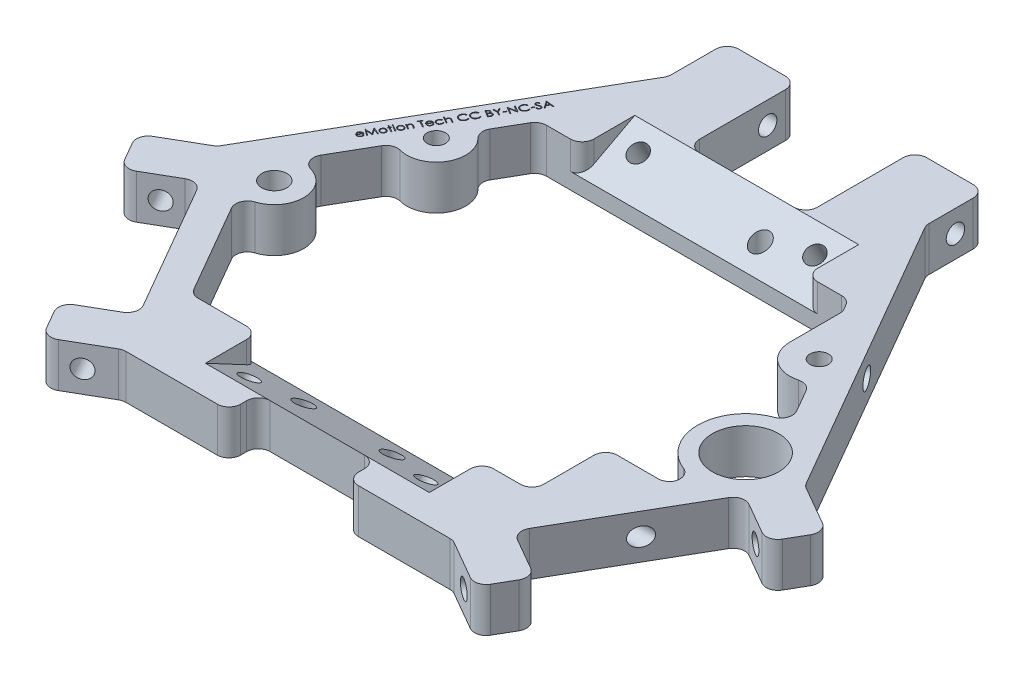
SolidWorks part; units mm, degrees
material "Alliage 1060"
ref_plane "Plan de face" through (0, 0, 0) normal (0, 0, 1) x (1, 0, 0)
ref_plane "Plan de dessus" through (0, 0, 0) normal (0, 1, 0) x (1, 0, 0)
ref_plane "Plan de droite" through (0, 0, 0) normal (1, 0, 0) x (0, 0, -1)
ref_axis "Axe1" through (0, 0, 0) along (0, 1, 0)
sketch "Esquisse2" plane through (0, 0, 0) normal (0, 1, 0) x (1, 0, 0)
  line L0 (17.5, 44) -> (-17.5, 44)
  line L1 (-17.5, 44) -> (-17.5, 36)
  line L2 (-17.5, 36) -> (-39.9269, -2.8446)
  line L3 (-39.9269, -2.8446) -> (-46.8551, -6.8446)
  line L4 (-46.8551, -6.8446) -> (-29.3551, -37.1554)
  line L5 (-29.3551, -37.1554) -> (-22.4269, -33.1554)
  line L6 (-22.4269, -33.1554) -> (22.4269, -33.1554)
  line L7 (0, 54.3424) -> (0, -64.0626) construction
  line L8 (17.5, 40) -> (-17.5, 40) construction
  line L10 (-28.7135, 16.5777) -> (21.5714, -12.4543) construction
  line L11 (20.1175, -29.1554) -> (-20.1175, -29.1554)
  line L12 (-20.1175, -29.1554) -> (-35.3081, -2.8446)
  line L13 (-35.3081, -2.8446) -> (-15.1906, 32)
  line L14 (-15.1906, 32) -> (15.1906, 32)
  line L16 (28.7135, 16.5777) -> (-21.5714, -12.4543) construction
  line L18 (35.3081, -2.8446) -> (15.1906, 32)
  line L19 (20.1175, -29.1554) -> (35.3081, -2.8446)
  line L20 (29.3551, -37.1554) -> (22.4269, -33.1554)
  line L21 (46.8551, -6.8446) -> (29.3551, -37.1554)
  line L22 (39.9269, -2.8446) -> (46.8551, -6.8446)
  line L23 (17.5, 36) -> (39.9269, -2.8446)
  line L24 (17.5, 44) -> (17.5, 36)
  dimension "D8" = 40
  dimension "D2" = 12
  dimension "D3" = 120
  dimension "D4" = 120
  dimension "D5" = 8
  dimension "D6" = 35
  dimension "D7" = 35
  dimension "D9" = 12
  dimension "D10" = 4
  dimension "D11" = 4
extrude "Boss.-Extru.2" add sketch "Esquisse2" along normal blind 6 contours L2 L3 L4 L5 L6 L20 L21 L22 L23 L24 L0 L1 | L13 L14 L18 L19 L11 L12
hole_wizard "Trou pour taraudage pour trou taraudé M32" positions "Esquisse6" profile "Esquisse5" hole size "M3" standard "ISO"
sketch "Esquisse6" plane through (-17.5, 0, 0) normal (-1, 0, 0) x (0, 0, 1)
  line L4 (-40, 0) -> (-40, 6) construction
  line L5 (-44, 0) -> (-36, 0) construction
  line L6 (-44, 6) -> (-36, 6) construction
  point P0 (-40, 3)
sketch "Esquisse5" plane through (-17.5, 3, -40) normal (0, 1, 0) x (0, 0, 1)
  line L0 (0, 0) -> (0, 10.7511)
  line L1 (0, 10.7511) -> (1.25, 10)
  line L2 (1.25, 10) -> (1.25, 0)
  line L5 (1.25, 0) -> (0, 0)
  line L10 (0, 10.7511) -> (-1.25, 10) construction
  line L11 (0, -6.35) -> (0, 107.95) construction
  dimension "Diamètre du perçage" = 2.5
  dimension "Profondeur du perçage" = 10
  dimension "Angle de pointe" = 118
mirror "Symétrie1" about plane through (0, 0, 0) normal (1, 0, 0) of "Trou pour taraudage pour trou taraudé M32"
pattern_circular "Répétition circulaire1" count 3 over 360 about axis through (0, 0, 0) along (0, 1, 0) of "Trou pour taraudage pour trou taraudé M32", "Symétrie1"
sketch "Esquisse8" plane through (0, 0, 0) normal (1, 0, 0) x (0, 0, -1)
  line L0 (-33.1554, 6) -> (-29.1554, 6)
  line L1 (-29.1554, 6) -> (-22, 2.1954)
  line L2 (-22, 2.1954) -> (-22, 0)
  line L3 (-33.1554, 0) -> (-33.1554, 6)
  line L5 (0, 0) -> (0, 21.2084) construction
  line L6 (33.1554, 0) -> (33.1554, 6)
  line L8 (29.1554, 6) -> (22, 2.1954)
  line L9 (33.1554, 6) -> (29.1554, 6)
  line L10 (-22, 0) -> (-33.1554, 0)
  line L11 (-6.8446, 0) -> (-37.1554, 0) construction
  line L12 (22, 0) -> (33.1554, 0)
  line L13 (22, 2.1954) -> (22, 0)
  dimension "D1" = 28
  dimension "D2" = 22
extrude "Boss.-Extru.3" add sketch "Esquisse8" along normal blind 15.2 and the other way blind 15.2
hole_wizard "Trou pour taraudage pour trou taraudé M33" positions "Esquisse11" profile "Esquisse10" hole size "M3" standard "ISO"
sketch "Esquisse11" plane through (0, -7.4079, -3.9389) normal (0, 0.8829, 0.4695) x (1, 0, 0)
  line L0 (-15.2, 20.4555) -> (15.2, 20.4555) construction
  line L1 (0, 0) -> (0, 21.5167) construction
  line L2 (0, 0) -> (0, 40.3955) construction
  point P2 (12, 25.4555)
  point P17 (-12, 25.4555)
  dimension "D1" = 5
  dimension "D2" = 12
sketch "Esquisse10" plane through (12, 4.5427, -26.4147) normal (1, 0, 0) x (0, -0.4695, 0.8829)
  line L0 (0, 0) -> (0, 10.7511)
  line L1 (0, 10.7511) -> (1.25, 10)
  line L2 (1.25, 10) -> (1.25, 0)
  line L5 (1.25, 0) -> (0, 0)
  line L10 (0, 10.7511) -> (-1.25, 10) construction
  line L11 (0, -6.35) -> (0, 107.95) construction
  dimension "Diamètre du perçage" = 2.5
  dimension "Profondeur du perçage" = 10
  dimension "Angle de pointe" = 118
sketch "Esquisse9" plane through (0, 6, 0) normal (0, 1, 0) x (1, 0, 0)
  line L0 (-8, 29.1554) -> (-8, 44)
  line L1 (0, 0) -> (74.807, 0) construction
  line L2 (17.5, 44) -> (-17.5, 44) construction
  line L3 (-8, 44) -> (8, 44)
  line L4 (8, 44) -> (8, 29.1554)
  line L5 (15.2, 29.1554) -> (-15.2, 29.1554) construction
  line L6 (8, 29.1554) -> (-8, 29.1554)
  line L7 (8, -44) -> (8, -29.1554)
  line L8 (-8, -44) -> (8, -44)
  line L9 (-8, -29.1554) -> (-8, -44)
  line L10 (8, -29.1554) -> (-8, -29.1554)
  line L16 (0, 44) -> (0, -44) construction
  dimension "D2" = 16
extrude "Enlèv. mat.-Extru.1" cut sketch "Esquisse9" against normal blind 15
sketch "Esquisse12" plane through (0, 6, 0) normal (0, 1, 0) x (1, 0, 0)
  line L0 (15.2, -22) -> (24.2487, -22)
  line L1 (20.1175, -29.1554) -> (35.3081, -2.8446) construction
  line L2 (-20.1175, -29.1554) -> (-15.2, -29.1554)
  line L3 (-15.2, -29.1554) -> (-15.2, -22)
  line L4 (0, 0) -> (0, -39.258) construction
  line L5 (15.2, -29.1554) -> (15.2, -22)
  line L6 (20.1175, -29.1554) -> (15.2, -29.1554)
  line L7 (24.2487, -22) -> (20.1175, -29.1554)
  line L8 (-15.2, -22) -> (-24.2487, -22)
  line L9 (15.2, 22) -> (-15.2, 22) construction
  line L10 (-20.1175, -29.1554) -> (-35.3081, -2.8446) construction
  line L11 (-24.2487, -22) -> (-20.1175, -29.1554)
  line L12 (-15.2, 22) -> (-15.2, 31.9837)
  line L13 (-15.2, 31.9837) -> (-20.9641, 22)
  line L14 (-35.3081, -2.8446) -> (-15.2, 31.9837) construction
  line L15 (-20.9641, 22) -> (-15.2, 22)
  line L17 (15.2, 31.9837) -> (20.9641, 22)
  line L18 (35.3081, -2.8446) -> (15.2, 31.9837) construction
  line L19 (20.9641, 22) -> (15.2, 22)
  line L20 (15.2, 22) -> (15.2, 31.9837)
  line L22 (15.2, -22) -> (-15.2, -22) construction
extrude "Boss.-Extru.4" add sketch "Esquisse12" against normal up to surface (6 mm away) up to face at (12, 0, -27.4144)
mirror "Symétrie2" about plane through (0, 0, 0) normal (0, 0, 1) of "Trou pour taraudage pour trou taraudé M33"
hole_wizard "Trou pour taraudage pour trou taraudé M34" positions "Esquisse21" profile "Esquisse20" hole size "M3" standard "ISO"
sketch "Esquisse21" plane through (0, 6, 0) normal (0, 1, 0) x (1, 0, 0)
  line L0 (0, 0) -> (27.2651, 0) construction
  point P64 (-6, -25)
  point P66 (6, -25)
  point P75 (6, 25)
  dimension "D1" = 25
  dimension "D4" = 6
  dimension "D5" = 6
  dimension "D6" = 25
sketch "Esquisse20" plane through (-6, 6, 25) normal (1, 0, 0) x (0, 0, 1)
  line L0 (0, 0) -> (0, 15.7511)
  line L1 (0, 15.7511) -> (1.25, 15)
  line L2 (1.25, 15) -> (1.25, 0)
  line L5 (1.25, 0) -> (0, 0)
  line L10 (0, 15.7511) -> (-1.25, 15) construction
  line L11 (0, -6.35) -> (0, 107.95) construction
  dimension "Diamètre du perçage" = 2.5
  dimension "Profondeur du perçage" = 15
  dimension "Angle de pointe" = 118
sketch "Esquisse22" plane through (0, 0, 0) normal (0, -1, 0) x (1, 0, 0)
  line L0 (22, -20.2058) -> (22, -13)
  line L1 (-35.3081, 2.8446) -> (-33.1937, -0.8177)
  line L2 (24.2487, 22) -> (35.3081, 2.8446) construction
  line L3 (28.119, -9.6074) -> (22, -20.2058)
  line L4 (30.0222, 12) -> (22, 12)
  line L5 (24.2487, 22) -> (35.3081, 2.8446) construction
  line L6 (22, 12) -> (22, 22)
  line L8 (22, 22) -> (24.2487, 22)
  line L9 (24.2487, 22) -> (30.0222, 12)
  line L10 (21.5, -17) -> (-12.566, -17) construction
  line L11 (22, 17) -> (-17.9641, 17) construction
  line L12 (0, 0) -> (0, -37.0001) construction
  line L13 (-35.3081, 2.8446) -> (-20.9641, -22) construction
  line L14 (-32.9792, 6.8783) -> (-35.3081, 2.8446)
  line L15 (-28.119, -9.6074) -> (-24.1214, -16.5314)
  line L16 (35.3081, 2.8446) -> (20.9641, -22) construction
  line L17 (31.4777, 9.479) -> (35.3081, 2.8446)
  line L18 (35.3081, 2.8446) -> (31.6505, -3.4906)
  line L19 (24.2487, 22) -> (15.2, 22) construction
  line L20 (-24.2487, 22) -> (-35.3081, 2.8446) construction
  arc A0 (-28.119, -9.6074) -> (-24.1214, -16.5314) centre (-26, -13) cw
  arc A1 (28.119, -9.6074) -> (22, -13) centre (26, -13) ccw
  arc A2 (31.4777, 9.479) -> (31.6505, -3.4906) centre (32, 3) ccw
  arc A3 (-32.9792, 6.8783) -> (-33.1937, -0.8177) centre (-32, 3) cw
  dimension "D4" = 4
  dimension "D5" = 4
  dimension "D6" = 6.5
  dimension "D8" = 4
  dimension "D1" = 17
  dimension "D2" = 17
  dimension "D3" = 22
  dimension "D7" = 3
  dimension "D9" = 13
  dimension "D10" = 26
  dimension "D11" = 32
  dimension "D12" = 32
  dimension "D13" = 26
extrude "Boss.-Extru.6" add sketch "Esquisse22" against normal up to surface (6 mm away) up to face at (20.405, 6, -0.4706)
hole_wizard "Trou pour taraudage pour trou taraudé M35" positions "Esquisse24" profile "Esquisse23" hole size "M3" standard "ISO"
sketch "Esquisse24" plane through (22, 0, 0) normal (-1, 0, 0) x (0, 0, 1)
  line L1 (16.9706, 3.0001) -> (0, -13.9704) construction
  line L2 (0, -13.9704) -> (-16.9706, 3.0001) construction
  line L4 (0, 0) -> (0, 45.8318) construction
  line L5 (22, 6) -> (12, 6) construction
  point P8 (16.9706, 3.0001)
  point P11 (-16.9706, 3.0001)
  point P51 (17, 6)
  dimension "D1" = 24
  dimension "D2" = 24
  dimension "D3" = 3
sketch "Esquisse23" plane through (22, 3.0001, 16.9706) normal (0, 1, 0) x (0, 0, 1)
  line L0 (0, 0) -> (0, 20.7511)
  line L1 (0, 20.7511) -> (1.25, 20)
  line L2 (1.25, 20) -> (1.25, 0)
  line L5 (1.25, 0) -> (0, 0)
  line L10 (0, 20.7511) -> (-1.25, 20) construction
  line L11 (0, -6.35) -> (0, 107.95) construction
  dimension "Diamètre du perçage" = 2.5
  dimension "Profondeur du perçage" = 20
  dimension "Angle de pointe" = 118
sketch "Esquisse25" plane through (0, 6, 0) normal (0, 1, 0) x (1, 0, 0)
  line L0 (32.3551, -31.9593) -> (43.8551, -12.0407)
  line L1 (43.8551, -12.0407) -> (36.9269, -8.0407)
  line L2 (36.9269, -8.0407) -> (25.4269, -27.9593)
  line L3 (25.4269, -27.9593) -> (32.3551, -31.9593)
  line L4 (29.3551, -37.1554) -> (22.4269, -33.1554) construction
  line L5 (39.9269, -2.8446) -> (46.8551, -6.8446) construction
  line L7 (30.0222, -12) -> (31.4777, -9.479) construction
  line L8 (0, 0) -> (0, -40.6615) construction
  line L9 (-25.4269, -27.9593) -> (-32.3551, -31.9593)
  line L10 (-36.9269, -8.0407) -> (-25.4269, -27.9593)
  line L11 (-43.8551, -12.0407) -> (-36.9269, -8.0407)
  line L12 (-32.3551, -31.9593) -> (-43.8551, -12.0407)
  line L13 (46.8551, -6.8446) -> (29.3551, -37.1554) construction
  dimension "D2" = 4
  dimension "D3" = 6
  dimension "D4" = 6
extrude "Enlèv. mat.-Extru.2" cut sketch "Esquisse25" against normal blind 10
hole_wizard "Trou pour taraudage pour trou taraudé M36" positions "Esquisse27" profile "Esquisse26" hole size "M3" standard "ISO"
sketch "Esquisse27" plane through (0, 0, 0) normal (0, -1, 0) x (-1, 0, 0)
  point P0 (26, 13)
  point P2 (-26, 13)
  dimension "D1" = 13
  dimension "D2" = 26
  dimension "D3" = 26
sketch "Esquisse26" plane through (-26, 0, -13) normal (1, 0, 0) x (0, 0, -1)
  line L0 (0, 0) -> (0, 15.7511)
  line L1 (0, 15.7511) -> (1.25, 15)
  line L2 (1.25, 15) -> (1.25, 0)
  line L5 (1.25, 0) -> (0, 0)
  line L10 (0, 15.7511) -> (-1.25, 15) construction
  line L11 (0, -6.35) -> (0, 107.95) construction
  dimension "Diamètre du perçage" = 2.5
  dimension "Profondeur du perçage" = 15
  dimension "Angle de pointe" = 118
hole_wizard "Dégagement M81" positions "Esquisse29" profile "Esquisse28" hole size "M8" standard "ISO"
sketch "Esquisse29" plane through (0, 0, 0) normal (0, -1, 0) x (-1, 0, 0)
  arc A0 (-31.4777, -9.479) -> (-31.6505, 3.4906) centre (-32, -3) ccw construction
  point P0 (-32, -3)
sketch "Esquisse28" plane through (32, 0, 3) normal (1, 0, 0) x (0, 0, -1)
  line L0 (0, 0) -> (0, 17.7039)
  line L1 (0, 17.7039) -> (4.5, 15)
  line L2 (4.5, 15) -> (4.5, 0)
  line L5 (4.5, 0) -> (0, 0)
  line L10 (0, 17.7039) -> (-4.5, 15) construction
  line L11 (0, -6.35) -> (0, 107.95) construction
  dimension "Diamètre du perçage" = 9
  dimension "Profondeur du perçage" = 15
  dimension "Angle de pointe" = 118
fillet "Congé1" radius 1.59 46 edges at (17.5, 3, -44) (-17.5, 3, -44) (-46.8551, 3, 6.8446) (-29.3551, 3, 37.1554) (29.3551, 3, 37.1554) (46.8551, 3, 6.8446) (-39.9269, 3, 2.8446) (-17.5, 3, -36) (17.5, 3, -36) (39.9269, 3, 2.8446) (22.4269, 3, 33.1554) (-22.4269, 3, 33.1554) (20.9641, 3, -22) (-20.9641, 3, -22) (-24.2487, 3, 22) (15.2, 4.0977, 22) (15.2, 4.0977, -22) (-15.2, 4.0977, -22) (-15.2, 4.0977, 22) (8, 3, -44) (-8, 3, -44) (8, 3, 33.1554) (-8, 3, 33.1554) (30.0222, 3, 12) (22, 3, 12) (22, 3, 22) (-24.1214, 3, -16.5314) (-28.119, 3, -9.6074) (-36.9269, 3, 8.0407) (-43.8551, 3, 12.0407) (-25.4269, 3, 27.9593) (-32.3551, 3, 31.9593) (43.8551, 3, 12.0407) (32.3551, 3, 31.9593) (25.4269, 3, 27.9593) (36.9269, 3, 8.0407) (31.6505, 3, -3.4906) (31.4777, 3, 9.479) (-32.9792, 3, 6.8783) (-33.1937, 3, -0.8177) (28.119, 3, -9.6074) (22, 3, -20.2058) (-8, 3, 29.1554) (8, 3, 29.1554) (-8, 3, -29.1554) (8, 3, -29.1554)
hole_wizard "Dégagement M31" positions "Esquisse31" profile "Esquisse30" hole size "M3" standard "ISO"
sketch "Esquisse31" plane through (0, 6, 0) normal (0, 1, 0) x (1, 0, 0)
  arc A0 (-30.7883, -6.8121) -> (-30.8977, 0.8451) centre (-32, -3) ccw construction
  point P0 (-32, -3)
sketch "Esquisse30" plane through (-32, 6, 3) normal (1, 0, 0) x (0, 0, 1)
  line L0 (0, 0) -> (0, 16.0215)
  line L1 (0, 16.0215) -> (1.7, 15)
  line L2 (1.7, 15) -> (1.7, 0)
  line L5 (1.7, 0) -> (0, 0)
  line L10 (0, 16.0215) -> (-1.7, 15) construction
  line L11 (0, -6.35) -> (0, 107.95) construction
  dimension "Diamètre du perçage" = 3.4
  dimension "Profondeur du perçage" = 15
  dimension "Angle de pointe" = 118
sketch "Esquisse32" plane through (0, 6, 0) normal (0, 1, 0) x (1, 0, 0)
  line L0 (-37.443, -2.5423) -> (-15.7837, 34.9727) construction
  line L1 (-17.713, 35.631) -> (-39.7139, -2.4756) construction
  text T0 "eMotion Tech CC BY-NC-SA" font "Century Gothic" height in points 4
  dimension "D1" = 2
extrude "Enlèv. mat.-Extru.3" cut sketch "Esquisse32" against normal blind 0.5
